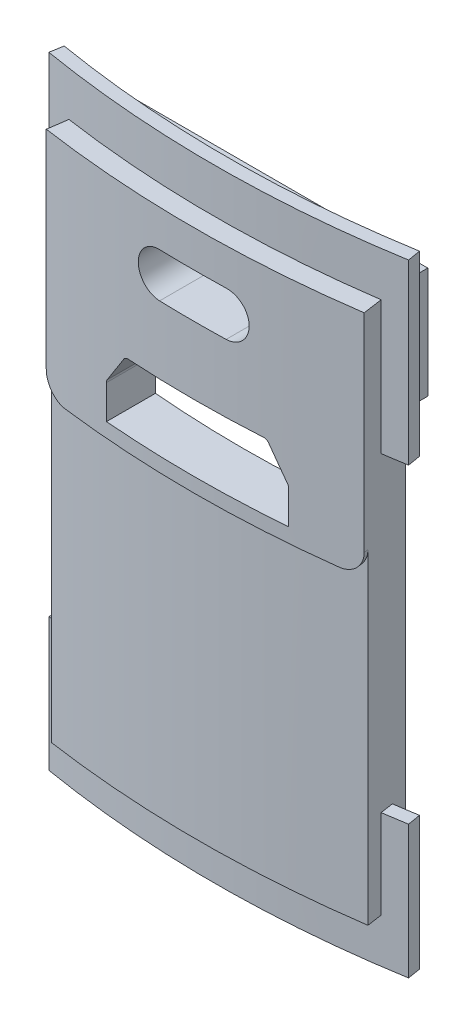
SolidWorks part; units mm, degrees
ref_plane "Front Plane" through (0, 0, 0) normal (0, 0, 1) x (1, 0, 0)
ref_plane "Top Plane" through (0, 0, 0) normal (0, 1, 0) x (1, 0, 0)
ref_plane "Right Plane" through (0, 0, 0) normal (1, 0, 0) x (0, 0, -1)
sketch "Эскиз1" plane through (0, 0, 0) normal (0, 1, 0) x (1, 0, 0)
  line L0 (-6.8438, 0.4925) -> (-7.1588, -1.6849)
  line L1 (6.8438, 0.4925) -> (7.1588, -1.6849)
  arc A0 (-6.8438, 0.4925) -> (6.8438, 0.4925) centre (0, 47.8) ccw
  arc A1 (-7.1588, -1.6849) -> (7.1588, -1.6849) centre (0, 47.8) ccw
extrude "Бобышка-Вытянуть1" add sketch "Эскиз1" along normal blind 24
sketch "Эскиз2" plane through (0, 0, 0) normal (0, 0, 1) x (1, 0, 0)
  line L8 (3.05, 17.3) -> (-3.05, 17.3)
  line L9 (4.0595, 15.9585) -> (3.2596, 17.1864)
  line L10 (-3.2596, 17.1864) -> (-4.0595, 15.9585)
  line L11 (-4.1, 14.788) -> (-4.1, 15.8219)
  line L12 (4.1, 14.788) -> (4.1, 15.8219)
  line L13 (-4.1, 14.3) -> (4.1, 14.3)
  line L14 (-4.1, 14.788) -> (-4.1, 14.3)
  line L15 (4.1, 14.788) -> (4.1, 14.3)
  line L16 (5.5897, 21.35) -> (-4.3329, 21.35) construction
  line L17 (-1.5632, 22.35) -> (-1.5632, 20.35) construction
  line L18 (1.4368, 22.35) -> (1.4368, 20.35) construction
  line L19 (-0.0632, 22.35) -> (0, 0) construction
  line L20 (-0.0632, 22.35) -> (1.4368, 22.35)
  line L21 (-0.0632, 22.35) -> (-1.5632, 22.35)
  line L23 (-1.5632, 20.35) -> (1.4368, 20.35)
  arc A4 (3.05, 17.3) -> (3.2596, 17.1864) centre (3.05, 17.0498) cw
  arc A5 (-3.2596, 17.1864) -> (-3.05, 17.3) centre (-3.05, 17.0498) cw
  arc A6 (-4.0595, 15.9585) -> (-4.1, 15.8219) centre (-3.8498, 15.8219) ccw
  arc A7 (4.0595, 15.9585) -> (4.1, 15.8219) centre (3.8498, 15.8219) cw
  arc A12 (-1.5632, 22.35) -> (-1.5632, 20.35) centre (-1.5632, 21.35) ccw
  arc A13 (1.4368, 20.35) -> (1.4368, 22.35) centre (1.4368, 21.35) ccw
  point P0 (0, 17.3)
  point P19 (0, 14.3)
  point P21 (-2.5632, 21.35)
  point P23 (2.4368, 21.35)
extrude "Вырез-Вытянуть2" cut sketch "Эскиз2" along normal blind 5 and the other way blind 5
sketch "Эскиз3" plane through (0, 24, 0) normal (0, 1, 0) x (1, 0, 0)
  line L1 (-8.0011, -0.0355) -> (-8.1001, -0.6272)
  line L3 (8.0011, -0.0355) -> (8.1001, -0.6272)
  line L4 (0, -0.7) -> (0, 0) construction
  line L5 (-6.8438, 0.4925) -> (-7.1588, -1.6849) construction
  line L6 (-6.9441, -0.2003) -> (-7.03, -0.7941)
  line L7 (7.1588, -1.6849) -> (6.8438, 0.4925) construction
  line L8 (7.03, -0.7941) -> (6.9441, -0.2003)
  arc A0 (-8.0011, -0.0355) -> (-6.9441, -0.2003) centre (0, 47.8) ccw
  arc A1 (-8.1001, -0.6272) -> (-7.03, -0.7941) centre (0, 47.8) ccw
  arc A2 (7.03, -0.7941) -> (8.1001, -0.6272) centre (0, 47.8) ccw
  arc A3 (6.9441, -0.2003) -> (8.0011, -0.0355) centre (0, 47.8) ccw
extrude "Бобышка-Вытянуть2" add sketch "Эскиз3" against normal up to surface (24 mm away) up to face at (0, 0, 0.8481)
sketch "Эскиз4" plane through (0, 24, 0) normal (0, 1, 0) x (1, 0, 0)
  line L0 (-8.0011, -0.0355) -> (-8.1001, -0.6272)
  line L2 (8.0011, -0.0355) -> (8.1001, -0.6272)
  line L3 (0, -0.7) -> (0, 0) construction
  arc A0 (-8.0011, -0.0355) -> (8.0011, -0.0355) centre (0, 47.8) ccw
  arc A1 (-8.1001, -0.6272) -> (8.1001, -0.6272) centre (0, 47.8) ccw
extrude "Бобышка-Вытянуть3" add sketch "Эскиз4" along normal blind 2
sketch "Эскиз5" plane through (0, 0, 0) normal (0, -1, 0) x (1, 0, 0)
  line L0 (8.0011, 0.0355) -> (8.1001, 0.6272)
  line L1 (-8.0011, 0.0355) -> (-8.1001, 0.6272)
  line L2 (0, 0.7) -> (0, 0) construction
  arc A0 (8.0011, 0.0355) -> (-8.0011, 0.0355) centre (0, -47.8) ccw
  arc A1 (8.1001, 0.6272) -> (-8.1001, 0.6272) centre (0, -47.8) ccw
extrude "Бобышка-Вытянуть4" add sketch "Эскиз5" along normal blind 2
sketch "Эскиз6" plane through (0, 0, 0) normal (0, -1, 0) x (1, 0, 0)
  line L0 (-7.1588, 1.6849) -> (-7.1302, 1.4869)
  line L1 (7.1588, 1.6849) -> (7.1302, 1.4869)
  arc A0 (7.1588, 1.6849) -> (-7.1588, 1.6849) centre (0, -47.8) ccw construction
  arc A1 (7.1588, 1.6849) -> (-7.1588, 1.6849) centre (0, -47.8) ccw
  arc A2 (7.1302, 1.4869) -> (-7.1302, 1.4869) centre (0, -47.8) ccw
  dimension "D1" = 0.2
extrude "Вырез-Вытянуть3" cut sketch "Эскиз6" against normal blind 13.65
fillet "Скругление1" radius 1 2 edges at (-7.1445, 13.65, 1.5859) (7.1445, 13.65, 1.5859)
sketch "Эскиз8" plane through (0, 26, 0) normal (0, 1, 0) x (1, 0, 0)
  line L0 (8.1001, -0.6272) -> (8.0011, -0.0355) construction
  line L1 (-8.0011, -0.0355) -> (-8.1001, -0.6272) construction
  line L2 (8.1001, -0.6272) -> (8.0011, -0.0355)
  line L3 (-8.0011, -0.0355) -> (-8.1001, -0.6272)
  line L4 (-6.9441, -0.2003) -> (-7.03, -0.7941)
  line L5 (6.9441, -0.2003) -> (7.03, -0.7941)
  arc A0 (-8.0011, -0.0355) -> (8.0011, -0.0355) centre (0, 47.8) ccw construction
  arc A1 (-8.1001, -0.6272) -> (8.1001, -0.6272) centre (0, 47.8) ccw construction
  arc A2 (-8.0011, -0.0355) -> (-6.9441, -0.2003) centre (0, 47.8) ccw
  arc A3 (-8.1001, -0.6272) -> (-7.03, -0.7941) centre (0, 47.8) ccw
  arc A4 (7.03, -0.7941) -> (8.1001, -0.6272) centre (0, 47.8) ccw
  arc A5 (6.9441, -0.2003) -> (8.0011, -0.0355) centre (0, 47.8) ccw
extrude "Вырез-Вытянуть5" cut sketch "Эскиз8" against normal blind 14 from offset 8 offset against normal yes
sketch "Эскиз9" plane through (0, 24, 0) normal (0, 1, 0) x (1, 0, 0)
  line L0 (-6.8438, 0.4925) -> (-6.8438, 1.4925)
  line L1 (6.8438, 0.4925) -> (6.8438, 1.4925)
  line L2 (6.8438, 1.4925) -> (-6.8438, 1.4925)
  arc A0 (-6.8438, 0.4925) -> (6.8438, 0.4925) centre (0, 47.8) ccw construction
  arc A1 (-6.8438, 0.4925) -> (6.8438, 0.4925) centre (0, 47.8) ccw
extrude "Бобышка-Вытянуть5" add sketch "Эскиз9" against normal blind 5
sketch "Эскиз10" plane through (0, 0, 0) normal (0, 0, 1) x (1, 0, 0)
  line L0 (1.4368, 20.35) -> (-1.5632, 20.35) construction
  line L1 (-1.5632, 22.35) -> (1.4368, 22.35) construction
  line L2 (1.4368, 20.35) -> (-1.5632, 20.35)
  line L3 (-1.5632, 22.35) -> (1.4368, 22.35)
  arc A2 (1.4368, 20.35) -> (1.4368, 22.35) centre (1.4368, 21.35) ccw construction
  arc A3 (-1.5632, 22.35) -> (-1.5632, 20.35) centre (-1.5632, 21.35) ccw construction
  arc A4 (1.4368, 20.35) -> (1.4368, 22.35) centre (1.4368, 21.35) ccw
  arc A5 (-1.5632, 22.35) -> (-1.5632, 20.35) centre (-1.5632, 21.35) ccw
extrude "Вырез-Вытянуть6" cut sketch "Эскиз10" against normal up to surface (1.4925 mm away) up to face at (0, 21.5, -1.4925)
